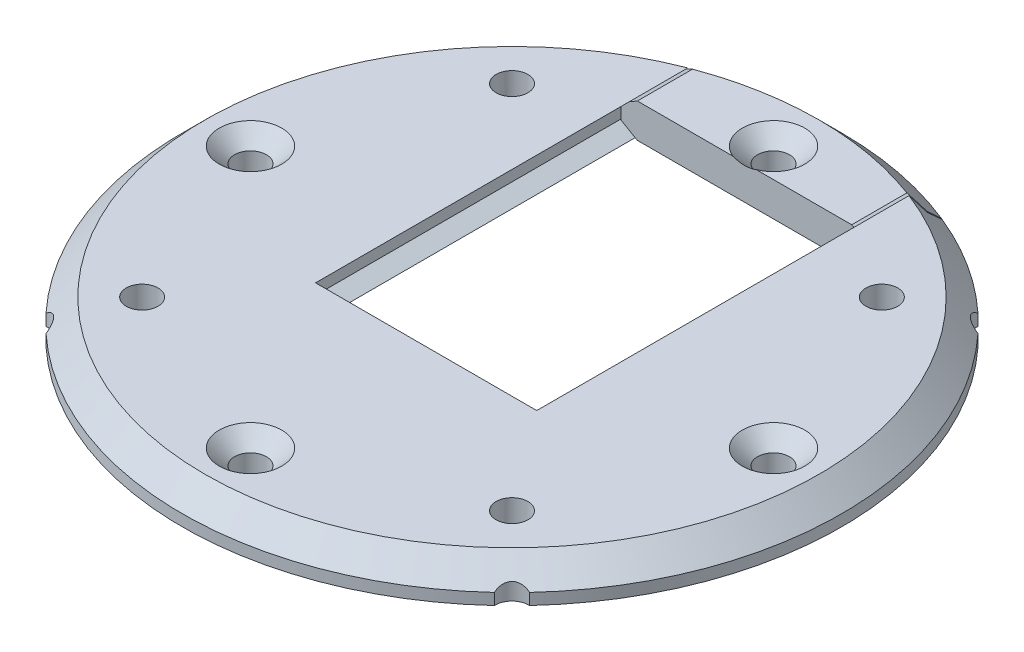
SolidWorks part; units mm, degrees
ref_plane "Front Plane" through (0, 0, 0) normal (0, 0, 1) x (1, 0, 0)
ref_plane "Top Plane" through (0, 0, 0) normal (0, 1, 0) x (1, 0, 0)
ref_plane "Right Plane" through (0, 0, 0) normal (1, 0, 0) x (0, 0, -1)
sketch "Sketch1" plane through (0, 0, 0) normal (0, 1, 0) x (1, 0, 0)
  circle A0 centre (0, 0) radius 29
  dimension "D1" = 58
extrude "Boss-Extrude1" add sketch "Sketch1" along normal mid plane 3
sketch "Sketch2" plane through (0, 1.5, 0) normal (0, 1, 0) x (1, 0, 0)
  line L0 (-11.025, 7.55) -> (-11.025, 29)
  line L1 (-11.025, -7.55) -> (11.025, -7.55)
  line L2 (-11.025, -7.55) -> (-11.025, 7.55)
  line L3 (-11.025, 7.55) -> (11.025, 7.55) construction
  line L4 (11.025, -7.55) -> (11.025, 7.55)
  line L5 (-11.025, -7.55) -> (11.025, 7.55) construction
  line L6 (-11.025, 7.55) -> (11.025, -7.55) construction
  line L7 (-11.025, 29) -> (11.025, 29)
  line L8 (11.025, 29) -> (11.025, 7.55)
  circle A0 centre (0, 0) radius 29 construction
  point P0 (0, 0)
  dimension "D1" = 7.55
  dimension "D2" = 22.05
extrude "Cut-Extrude1" cut sketch "Sketch2" against normal through all
sketch "Sketch3" plane through (0, 0, 7.55) normal (0, 0, -1) x (-1, 0, 0)
  line L0 (0, -1.5) -> (0, 1.5) construction
  line L1 (11.025, -1.5) -> (-11.025, -1.5) construction
  line L2 (11.025, 1.5) -> (-11.025, 1.5) construction
  line L3 (-11.525, -1.5) -> (-9.726, -1.5)
  line L5 (-9.726, -1.5) -> (-11.025, -0.75)
  line L6 (-11.025, -1.5) -> (-11.025, 1.5) construction
  line L7 (-11.025, -0.75) -> (-11.025, 0.75)
  line L8 (-11.025, 0.75) -> (-9.726, 1.5)
  line L9 (-9.726, 1.5) -> (-11.525, 1.5)
  line L10 (29, 1.5) -> (-29, 1.5) construction
  line L11 (-11.525, 1.5) -> (-11.525, -1.5)
  line L12 (-29, -1.5) -> (29, -1.5) construction
  line L13 (-11.025, -1.5) -> (-11.025, 1.5) construction
  line L21 (11.525, 1.5) -> (11.525, -1.5)
  line L22 (9.726, 1.5) -> (11.525, 1.5)
  line L23 (11.025, 0.75) -> (9.726, 1.5)
  line L24 (11.025, -0.75) -> (11.025, 0.75)
  line L25 (9.726, -1.5) -> (11.025, -0.75)
  line L26 (11.525, -1.5) -> (9.726, -1.5)
  point P10 (-11.025, 0)
  dimension "D1" = 0.5
  dimension "D2" = 60
  dimension "D3" = 1.5
extrude "Boss-Extrude2" add sketch "Sketch3" along normal up to surface (34.1615 mm away) up to face at (0, 0, 1.0887)
ref_plane "Plane1" through (0, 0, -20.45) normal (0, 0, -1) x (-1, 0, 0)
sketch "Sketch6" plane through (0, 0, -20.45) normal (0, 0, -1) x (-1, 0, 0)
  line L0 (-9.726, -1.5) -> (-11.025, -0.75) construction
  line L1 (-11.025, -0.75) -> (-11.025, 0.75) construction
  line L2 (-11.025, 0.75) -> (-9.726, 1.5) construction
  line L3 (-9.726, -1.5) -> (-11.025, -0.75) construction
  line L4 (-11.025, -0.75) -> (-11.025, 0.75) construction
  line L5 (-11.025, 0.75) -> (-9.726, 1.5) construction
  line L6 (-9.426, 1.5) -> (-10.875, 0.6634)
  line L7 (9.726, 1.5) -> (-9.726, 1.5) construction
  line L8 (-10.875, 0.6634) -> (-10.875, -0.6634)
  line L9 (-10.875, -0.6634) -> (-9.426, -1.5)
  line L10 (9.726, -1.5) -> (-9.726, -1.5) construction
  line L11 (0, 0) -> (0, 1.5) construction
  line L12 (10.875, -0.6634) -> (9.426, -1.5)
  line L13 (10.875, 0.6634) -> (10.875, -0.6634)
  line L14 (9.426, 1.5) -> (10.875, 0.6634)
  line L15 (-10.875, 0.6634) -> (-10.95, 0.7933) construction
  line L16 (-10.875, 0.6634) -> (-11.025, 0.6634) construction
  line L17 (10.875, -0.6634) -> (9.426, -1.5)
  line L18 (10.875, 0.6634) -> (10.875, -0.6634)
  line L19 (9.426, 1.5) -> (10.875, 0.6634)
  line L20 (-9.426, 1.5) -> (9.426, 1.5)
  line L21 (9.426, -1.5) -> (-9.426, -1.5)
  dimension "D1" = 0.15
extrude "Boss-Extrude3" add sketch "Sketch6" along normal up to surface (6.4337 mm away) separate body contours L21 L12 L13 L14 L20 L6 L8 L9 region at (0, 0, -20.45) up to face at (0, 0, -12.9953)
chamfer "Chamfer1" distance 2 angle 45 1 edges at (0, 1.5, 29)
chamfer "Chamfer2" distance 2 angle 45 2 edges at (-4.7783, 1.5, -28.6036) (4.7783, 1.5, -28.6036)
sketch "Sketch5" plane through (0, 1.5, 0) normal (0, 1, 0) x (1, 0, 0)
  circle A0 centre (0, 0) radius 23 construction
  circle A1 centre (0, 23) radius 1.4
  circle A2 centre (16.2635, 16.2635) radius 1.4
  circle A3 centre (23, 0) radius 1.4
  circle A4 centre (16.2635, -16.2635) radius 1.4
  circle A5 centre (0, -23) radius 1.4
  circle A6 centre (-16.2635, -16.2635) radius 1.4
  circle A7 centre (-23, 0) radius 1.4
  circle A8 centre (-16.2635, 16.2635) radius 1.4
  point P21 (0, 0)
  dimension "D1" = 46
  dimension "D2" = 2.8
  dimension "D3" = 8
extrude "Cut-Extrude2" cut sketch "Sketch5" against normal through all
hole_wizard "CSK for M2.5 Flat Head Machine Screw1" positions "Sketch7" profile "Sketch8" countersink size "M2.5" standard "ANSI Metric" end condition through all
sketch "Sketch7" plane through (0, 1.5, 0) normal (0, 1, 0) x (1, 0, 0)
  point P13 (0, 23)
  point P16 (23, 0)
  point P19 (0, -23)
  point P22 (-23, 0)
sketch "Sketch8" plane through (0, 1.5, -23) normal (1, 0, 0) x (0, 0, 1)
  line L0 (0, 0) -> (0, 3)
  line L1 (0, 3) -> (1.35, 3)
  line L2 (1.35, 3) -> (1.35, 1.4)
  line L3 (1.35, 1.4) -> (2.75, 0)
  line L5 (2.75, 0) -> (0, 0)
  line L6 (-1.35, 1.4) -> (-2.75, 0) construction
  line L11 (0, -6.35) -> (0, 107.95) construction
  dimension "Thru Hole Dia." = 2.7
  dimension "Thru Hole Depth" = 3
  dimension "Near C'Sink Dia." = 5.5
  dimension "Near C'Sink Angle" = 90
sketch "Sketch10" [suppressed] plane through (0, 1.5, 0) normal (0, 1, 0) x (1, 0, 0)
  line L0 (0, 0) -> (0, -30) construction
  line L1 (15, -12.5) -> (11.5, -12.5) construction
  line L6 (-15, 12.5) -> (-11.5, 12.5) construction
  line L7 (-15, 12.5) -> (-15, -12.5) construction
  line L8 (-15, -12.5) -> (-11.5, -12.5) construction
  line L9 (-11.5, 12.5) -> (-11.5, -12.5) construction
  line L10 (-11.5, -12.5) -> (11.5, -12.5) construction
  line L11 (-11.5, -12.5) -> (-11.5, -9) construction
  line L12 (-11.5, -9) -> (11.5, -9) construction
  line L13 (11.5, -12.5) -> (11.5, -9) construction
  line L14 (11.5, 12.5) -> (11.5, -12.5) construction
  line L15 (15, 12.5) -> (11.5, 12.5) construction
  line L16 (15, 12.5) -> (15, -12.5) construction
  line L17 (0, 0) -> (-11.5, 0) construction
  line L18 (-11.5, -9) -> (-11.5, 12.5)
  line L19 (-11.5, 12.5) -> (-15, 12.5)
  line L20 (-15, 12.5) -> (-15, -12.5)
  line L21 (-15, -12.5) -> (15, -12.5)
  line L22 (15, -12.5) -> (15, 12.5)
  line L23 (15, 12.5) -> (11.5, 12.5)
  line L24 (11.5, 12.5) -> (11.5, -9)
  line L25 (11.5, -9) -> (-11.5, -9)
  arc A0 (-11.025, 27.9007) -> (11.025, 27.9007) centre (0, 0) ccw construction
  point P18 (-11.5, 0)
  point P36 (0, -12.5)
  point P37 (0, -9)
  dimension "D5" = 30
  dimension "D1" = 3.5
  dimension "D2" = 3.5
  dimension "D3" = 23
  dimension "D4" = 25
  dimension "D6" = 25
extrude "Boss-Extrude4" [suppressed] add sketch "Sketch10" along normal blind 5
sketch "Sketch11" [suppressed] plane through (0, 0, 9) normal (0, 0, -1) x (-1, 0, 0)
  line L0 (-11.5, 6.5) -> (11.5, 6.5) construction
  line L1 (0, 6.5) -> (-2.45, 5.0855) construction
  line L2 (-2.45, 5.0855) -> (-2.45, 2.2565)
  line L3 (-2.45, 2.2565) -> (0, 0.842)
  line L4 (0, 0.842) -> (2.45, 2.2565)
  line L5 (2.45, 2.2565) -> (2.45, 5.0855)
  line L6 (2.45, 5.0855) -> (0, 6.5) construction
  line L7 (-2.45, 5.0855) -> (-2.45, 6.5)
  line L8 (-2.45, 6.5) -> (2.45, 6.5)
  line L9 (2.45, 6.5) -> (2.45, 5.0855)
  circle A0 centre (0, 3.671) radius 2.45 construction
  dimension "D1" = 4.9
extrude "Cut-Extrude3" [suppressed] cut sketch "Sketch11" against normal blind 2
chamfer "Chamfer3" [suppressed] distance 3.5 angle 45
sketch "Sketch12" [suppressed] plane through (-11.5, 0, 0) normal (1, 0, 0) x (0, 0, -1)
  line L0 (0, 0) -> (0, 6.5) construction
  line L1 (-9, 6.5) -> (9, 6.5) construction
  line L2 (-9, 5.0855) -> (-9, 6.5)
  line L3 (-6.55, 6.5) -> (-9, 5.0855) construction
  line L4 (-9, 5.0855) -> (-9, 2.2565)
  line L5 (-9, 2.2565) -> (-6.55, 0.842)
  line L6 (-6.55, 0.842) -> (-4.1, 2.2565)
  line L7 (-4.1, 2.2565) -> (-4.1, 5.0855)
  line L8 (-4.1, 5.0855) -> (-6.55, 6.5) construction
  line L9 (-9, 6.5) -> (-4.1, 6.5)
  line L10 (-4.1, 6.5) -> (-4.1, 5.0855)
  line L11 (9, 6.5) -> (4.1, 6.5)
  line L12 (9, 5.0855) -> (9, 6.5)
  line L13 (9, 5.0855) -> (9, 2.2565)
  line L14 (9, 2.2565) -> (6.55, 0.842)
  line L15 (6.55, 0.842) -> (4.1, 2.2565)
  line L16 (4.1, 2.2565) -> (4.1, 5.0855)
  line L17 (4.1, 6.5) -> (4.1, 5.0855)
  line L18 (-9, 6.5) -> (-9, 1.5) construction
  circle A0 centre (-6.55, 3.671) radius 2.45 construction
  dimension "D2" = 4.9
extrude "Cut-Extrude4" [suppressed] cut sketch "Sketch12" against normal blind 2
mirror "Mirror1" [suppressed] about plane through (0, 0, 0) normal (1, 0, 0)
sketch "Sketch13" [suppressed] plane through (0, 0, 11) normal (0, 0, -1) x (-1, 0, 0)
  circle A0 centre (0, 3.671) radius 1.4
  dimension "D1" = 2.8
extrude "Cut-Extrude5" [suppressed] cut sketch "Sketch13" against normal blind 2
sketch "Sketch14" [suppressed] plane through (-15, 0, 0) normal (-1, 0, 0) x (0, 0, 1)
  line L0 (0, 6.5) -> (0, 0) construction
  line L1 (-9, 6.5) -> (9, 6.5) construction
  circle A0 centre (6.55, 3.671) radius 1.4
  circle A1 centre (-6.55, 3.671) radius 1.4
  dimension "D1" = 2.8
extrude "Cut-Extrude6" [suppressed] cut sketch "Sketch14" against normal through all both and the other way through all
sketch "Sketch15" plane through (0, 0, 0) normal (0, 1, 0) x (1, 0, 0)
  line L0 (0, 0) -> (-20.5061, 20.5061) construction
  line L1 (0, 0) -> (0, -29) construction
  arc A0 (-11.025, 26.8226) -> (11.025, 26.8226) centre (0, 0) ccw construction
  circle A1 centre (-21.2132, 21.2132) radius 1.5
  circle A2 centre (21.2132, 21.2132) radius 1.5
  circle A3 centre (21.2132, -21.2132) radius 1.5
  circle A4 centre (-21.2132, -21.2132) radius 1.5
  point P17 (0, 0)
  dimension "D2" = 3
  dimension "D1" = 135
  dimension "D3" = 1
  dimension "D4" = 4
extrude "Cut-Extrude7" cut sketch "Sketch15" against normal through all
equation "\"m2.5 width\"= 4.9mm"
equation "\"D1@Sketch11\"=\"m2.5 width\""
equation "\"D2@Sketch12\"=\"m2.5 width\""
